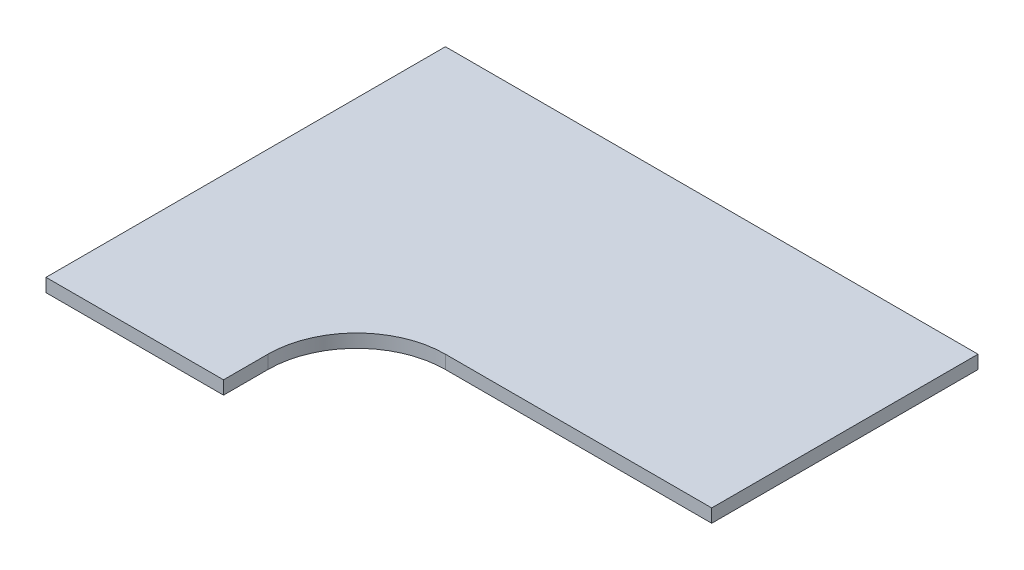
SolidWorks part; units mm, degrees
ref_plane "Front Plane" through (0, 0, 0) normal (0, 0, 1) x (1, 0, 0)
ref_plane "Top Plane" through (0, 0, 0) normal (0, 1, 0) x (1, 0, 0)
ref_plane "Right Plane" through (0, 0, 0) normal (1, 0, 0) x (0, 0, -1)
sketch "Sketch1" plane through (0, 0, 0) normal (0, 1, 0) x (1, 0, 0)
  line L0 (0, 0) -> (0, -900)
  line L1 (0, 0) -> (1200, 0)
  line L2 (1200, 0) -> (1200, -600)
  line L3 (1200, -600) -> (600, -600)
  line L4 (400, -800) -> (400, -900)
  line L5 (400, -900) -> (0, -900)
  arc A0 (600, -600) -> (400, -800) centre (600, -800) ccw
  dimension "D5" = 200
  dimension "D1" = 900
  dimension "D2" = 1200
  dimension "D3" = 600
  dimension "D4" = 400
extrude "Boss-Extrude1" add sketch "Sketch1" along normal blind 30
